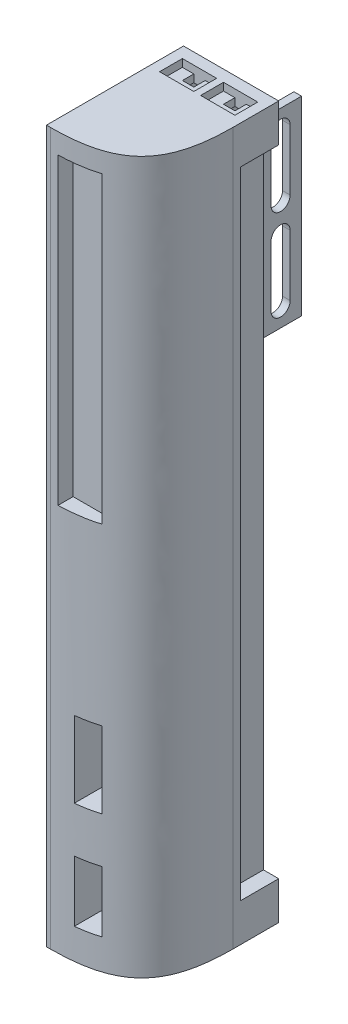
SolidWorks part; units mm, degrees
ref_plane "Front Plane" through (0, 0, 0) normal (0, 0, 1) x (1, 0, 0)
ref_plane "Top Plane" through (0, 0, 0) normal (0, 1, 0) x (1, 0, 0)
ref_plane "Right Plane" through (0, 0, 0) normal (1, 0, 0) x (0, 0, -1)
sketch "Sketch1" plane through (0, 0, 0) normal (0, 1, 0) x (1, 0, 0)
  line L1 (0, 0) -> (25, 0)
  line L2 (0, 0) -> (0, 36)
  line L3 (0, 36) -> (25, 36)
  line L4 (25, 0) -> (25, 36)
  dimension "D1" = 36
  dimension "D2" = 25
extrude "Boss-Extrude1" add sketch "Sketch1" along normal blind 186.9
fillet "Fillet1" radius 24 1 edges at (25, 93.45, 0) conic rho 0.55
sketch "Sketch2" plane through (0, 0, 0) normal (-1, 0, 0) x (0, 0, 1)
  line L0 (-24, 0) -> (0, 0) construction
  line L1 (-6.2, 83.2) -> (-1.2, 83.2)
  line L2 (-6.2, 83.2) -> (-6.2, 73.2)
  line L3 (-6.2, 73.2) -> (-1.2, 73.2)
  line L4 (-1.2, 83.2) -> (-1.2, 73.2)
  line L5 (0, 186.9) -> (0, 0) construction
  dimension "D1" = 73.2
  dimension "D2" = 1.2
  dimension "D3" = 5
  dimension "D4" = 10
extrude "Cut-Extrude1" cut sketch "Sketch2" against normal blind 4
sketch "Sketch3" plane through (0, 0, 0) normal (-1, 0, 0) x (0, 0, 1)
  line L1 (-14, 33.2) -> (-6, 33.2)
  line L2 (-14, 33.2) -> (-14, 28)
  line L3 (-14, 28) -> (-6, 28)
  line L4 (-6, 33.2) -> (-6, 28)
  line L5 (-36, 0) -> (0, 0) construction
  line L6 (0, 186.9) -> (0, 0) construction
  line L8 (-22, 33.2) -> (-30, 33.2)
  line L9 (-22, 33.2) -> (-22, 28)
  line L10 (-22, 28) -> (-30, 28)
  line L11 (-30, 33.2) -> (-30, 28)
  line L12 (-6, 61.2) -> (-14, 61.2)
  line L13 (-6, 61.2) -> (-6, 66.8)
  line L14 (-6, 66.8) -> (-14, 66.8)
  line L15 (-14, 61.2) -> (-14, 66.8)
  line L16 (-22, 66.8) -> (-30, 66.8)
  line L17 (-22, 66.8) -> (-22, 61.2)
  line L18 (-22, 61.2) -> (-30, 61.2)
  line L19 (-30, 66.8) -> (-30, 61.2)
  dimension "D1" = 28
  dimension "D2" = 6
  dimension "D3" = 8
  dimension "D4" = 5.2
  dimension "D5" = 8
  dimension "D6" = 8
  dimension "D7" = 28
  dimension "D8" = 5.6
  dimension "D9" = 8
  dimension "D10" = 6
  dimension "D11" = 8
  dimension "D12" = 5.6
  dimension "D13" = 8
extrude "Cut-Extrude2" cut sketch "Sketch3" against normal blind 10
sketch "Sketch4" plane through (0, 0, 0) normal (-1, 0, 0) x (0, 0, 1)
  line L0 (-36, 0) -> (0, 0) construction
  line L1 (-26, 160) -> (-67, 160)
  line L2 (-26, 160) -> (-26, 110)
  line L3 (-26, 110) -> (-67, 110)
  line L4 (-67, 160) -> (-67, 110)
  line L5 (-36, 186.9) -> (-36, 0) construction
  dimension "D1" = 160
  dimension "D2" = 10
  dimension "D3" = 31
  dimension "D4" = 110
extrude "Boss-Extrude2" add sketch "Sketch4" along normal blind 2
sketch "Sketch5" plane through (-2, 0, 0) normal (-1, 0, 0) x (0, 0, 1)
  line L0 (-67, 110) -> (-26, 110) construction
  line L1 (-67, 160) -> (-67, 110) construction
  line L4 (-59, 131) -> (-59, 115)
  line L6 (-64, 131) -> (-64, 115)
  line L7 (-26, 160) -> (-67, 160) construction
  line L9 (-64, 139) -> (-64, 155)
  line L11 (-59, 139) -> (-59, 155)
  arc A0 (-64, 115) -> (-59, 115) centre (-61.5, 115) ccw
  arc A2 (-59, 131) -> (-64, 131) centre (-61.5, 131) ccw
  arc A3 (-59, 155) -> (-64, 155) centre (-61.5, 155) ccw
  arc A4 (-64, 139) -> (-59, 139) centre (-61.5, 139) ccw
  dimension "D1" = 5
  dimension "D4" = 16
  dimension "D5" = 16
  dimension "D2" = 5
  dimension "D3" = 5.5
  dimension "D6" = 5
extrude "Cut-Extrude3" cut sketch "Sketch5" against normal up to next
chamfer "Chamfer1" distance 16 angle 45 1 edges at (0, 135, -36)
sketch "Sketch6" plane through (0, 0, -36) normal (0, 0, -1) x (-1, 0, 0)
  line L0 (-25, 186.9) -> (-25, 0) construction
  line L1 (-21, 182.9) -> (-15, 182.9)
  line L2 (-21, 182.9) -> (-21, 178.9)
  line L3 (-21, 178.9) -> (-15, 178.9)
  line L4 (-15, 182.9) -> (-15, 178.9)
  line L5 (-25, 186.9) -> (0, 186.9) construction
  line L6 (-1, 186.9) -> (-25, 186.9) construction
  line L7 (-10.2, 182.9) -> (-4.2, 182.9)
  line L8 (-10.2, 182.9) -> (-10.2, 178.9)
  line L9 (-10.2, 178.9) -> (-4.2, 178.9)
  line L10 (-4.2, 182.9) -> (-4.2, 178.9)
  dimension "D1" = 4
  dimension "D2" = 4
  dimension "D3" = 4
  dimension "D4" = 6
  dimension "D5" = 6
  dimension "D6" = 4.8
  dimension "D7" = 4
extrude "Cut-Extrude4" cut sketch "Sketch6" against normal blind 9
sketch "Sketch7" plane through (0, 186.9, 0) normal (0, 1, 0) x (1, 0, 0)
  line L0 (25, 24) -> (25, 36) construction
  line L1 (19.5, 33) -> (16.5, 33)
  line L2 (19.5, 33) -> (19.5, 30)
  line L3 (19.5, 30) -> (16.5, 30)
  line L4 (16.5, 33) -> (16.5, 30)
  line L5 (25, 36) -> (0, 36) construction
  line L7 (8.7, 33) -> (5.7, 33)
  line L8 (8.7, 33) -> (8.7, 30)
  line L9 (8.7, 30) -> (5.7, 30)
  line L10 (5.7, 33) -> (5.7, 30)
  dimension "D1" = 5.5
  dimension "D2" = 3
  dimension "D3" = 3
  dimension "D4" = 3
  dimension "D5" = 3
  dimension "D6" = 3
  dimension "D7" = 3
  dimension "D8" = 7.8
extrude "Cut-Extrude5" cut sketch "Sketch7" against normal blind 10
sketch "Sketch8" plane through (0, 0, 0) normal (0, -1, 0) x (1, 0, 0)
  line L0 (25, -36) -> (0, -36) construction
  line L1 (3, -5) -> (7, -5)
  line L2 (3, -5) -> (3, -33)
  line L3 (3, -33) -> (7, -33)
  line L4 (7, -5) -> (7, -29)
  line L5 (0, -36) -> (0, 0) construction
  line L6 (25, -24) -> (25, -36) construction
  line L7 (7, -33) -> (21, -33)
  line L9 (7, -29) -> (21, -29)
  line L10 (21, -33) -> (21, -29)
  dimension "D1" = 5
  dimension "D2" = 3
  dimension "D3" = 3
  dimension "D4" = 4
  dimension "D5" = 4
  dimension "D6" = 4
  dimension "D7" = 14
  dimension "D8" = 28
extrude "Boss-Extrude3" add sketch "Sketch8" along normal blind 4
sketch "Sketch9" plane through (0, 0, 0) normal (0, -1, 0) x (1, 0, 0)
  line L0 (21, -29) -> (7, -29) construction
  line L1 (7, -29) -> (7, -5) construction
  circle A0 centre (14, -22) radius 2
  dimension "D1" = 4
  dimension "D2" = 7
  dimension "D3" = 7
extrude "Cut-Extrude6" cut sketch "Sketch9" against normal blind 5
sketch "Sketch10" plane through (0, 0, 0) normal (0, -1, 0) x (1, 0, 0)
  line L0 (7, -29) -> (7, -5) construction
  circle A0 centre (14, -12) radius 1.5
  circle A1 centre (14, -22) radius 2 construction
  dimension "D1" = 7
  dimension "D2" = 10
  dimension "D3" = 3
extrude "Cut-Extrude7" cut sketch "Sketch10" against normal blind 4
sketch "Sketch11" plane through (0, 0, 0) normal (0, 0, 1) x (1, 0, 0)
  line L0 (0, 186.9) -> (0, 0) construction
  line L1 (7, 24) -> (13, 24)
  line L2 (7, 24) -> (7, 8)
  line L3 (7, 8) -> (13, 8)
  line L4 (13, 24) -> (13, 8)
  line L5 (0, 0) -> (1, 0) construction
  line L7 (7, 36) -> (13, 36)
  line L8 (7, 36) -> (7, 56)
  line L9 (7, 56) -> (13, 56)
  line L10 (13, 36) -> (13, 56)
  dimension "D1" = 7
  dimension "D2" = 8
  dimension "D3" = 16
  dimension "D4" = 6
  dimension "D5" = 12
  dimension "D6" = 6
  dimension "D7" = 20
  dimension "D8" = 7
extrude "Cut-Extrude8" cut sketch "Sketch11" against normal blind 8
sketch "Sketch12" plane through (0, 0, 0) normal (0, 0, 1) x (1, 0, 0)
  line L0 (0, 186.9) -> (0, 0) construction
  line L1 (3, 181.6) -> (13, 181.6)
  line L2 (3, 181.6) -> (3, 101.9)
  line L3 (3, 101.9) -> (13, 101.9)
  line L4 (13, 181.6) -> (13, 101.9)
  line L5 (25, 186.9) -> (1, 186.9) construction
  dimension "D1" = 3
  dimension "D2" = 5.3
  dimension "D3" = 10
  dimension "D4" = 79.7
extrude "Cut-Extrude9" cut sketch "Sketch12" against normal blind 4
sketch "Sketch13" plane through (25, 0, 0) normal (1, 0, 0) x (0, 0, -1)
  line L0 (36, 186.9) -> (36, 0) construction
  line L1 (36, 176.9) -> (26, 176.9)
  line L2 (36, 176.9) -> (36, 10)
  line L3 (36, 10) -> (26, 10)
  line L4 (26, 176.9) -> (26, 10)
  line L5 (24, 186.9) -> (36, 186.9) construction
  line L6 (24, 0) -> (36, 0) construction
  dimension "D1" = 10
  dimension "D2" = 10
  dimension "D3" = 10
extrude "Cut-Extrude10" cut sketch "Sketch13" against normal blind 4
sketch "Sketch14" plane through (0, 186.9, 0) normal (0, 1, 0) x (1, 0, 0)
  line L0 (5.7, 33) -> (5.7, 30) construction
  line L1 (2.7, 33) -> (11.7, 33)
  line L2 (2.7, 33) -> (2.7, 27)
  line L3 (2.7, 27) -> (11.7, 27)
  line L4 (11.7, 33) -> (11.7, 27)
  line L5 (8.7, 30) -> (8.7, 33) construction
  line L6 (8.7, 33) -> (5.7, 33) construction
  line L7 (5.7, 30) -> (8.7, 30) construction
  line L8 (19.5, 33) -> (16.5, 33) construction
  line L9 (13.5, 33) -> (22.5, 33)
  line L10 (13.5, 33) -> (13.5, 27)
  line L11 (13.5, 27) -> (22.5, 27)
  line L12 (22.5, 33) -> (22.5, 27)
  line L13 (16.5, 33) -> (16.5, 30) construction
  line L14 (19.5, 30) -> (19.5, 33) construction
  line L15 (16.5, 30) -> (19.5, 30) construction
  dimension "D1" = 3
  dimension "D2" = 3
  dimension "D3" = 0
  dimension "D4" = 3
  dimension "D5" = 0
  dimension "D6" = 3
  dimension "D7" = 3
  dimension "D8" = 3
extrude "Cut-Extrude11" cut sketch "Sketch14" against normal blind 2
